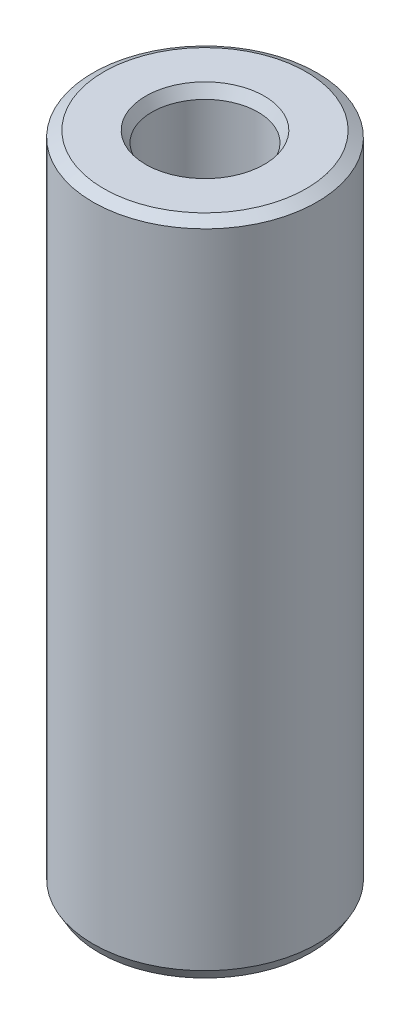
SolidWorks part; units mm, degrees
ref_plane "Front Plane" through (0, 0, 0) normal (0, 0, 1) x (1, 0, 0)
ref_plane "Top Plane" through (0, 0, 0) normal (0, 1, 0) x (1, 0, 0)
ref_plane "Right Plane" through (0, 0, 0) normal (1, 0, 0) x (0, 0, -1)
sketch "Sketch1" plane through (0, 0, 0) normal (0, 1, 0) x (1, 0, 0)
  circle A0 centre (0, 0) radius 52.5
  dimension "SLEEVE_OD" = 105
extrude "Boss-Extrude1" add sketch "Sketch1" along normal blind 309.0601
sketch "Sketch2" plane through (0, 0, 0) normal (0, 1, 0) x (1, 0, 0)
  circle A0 centre (0, 0) radius 24.8714
  dimension "BORE_D" = 49.7428
extrude "Cut-Extrude1" cut sketch "Sketch2" along normal through all
chamfer "Chamfer1" distance 2.9194 angle 60 4 edges at (0, 309.0601, 24.8714) (0, 0, 24.8714) (0, 0, 52.5) (0, 309.0601, 52.5) first distance on face at (0, 309.0601, 24.8714) first distance on face at (0, 0, 24.8714) first distance on face at (0, 309.0601, 52.5)
